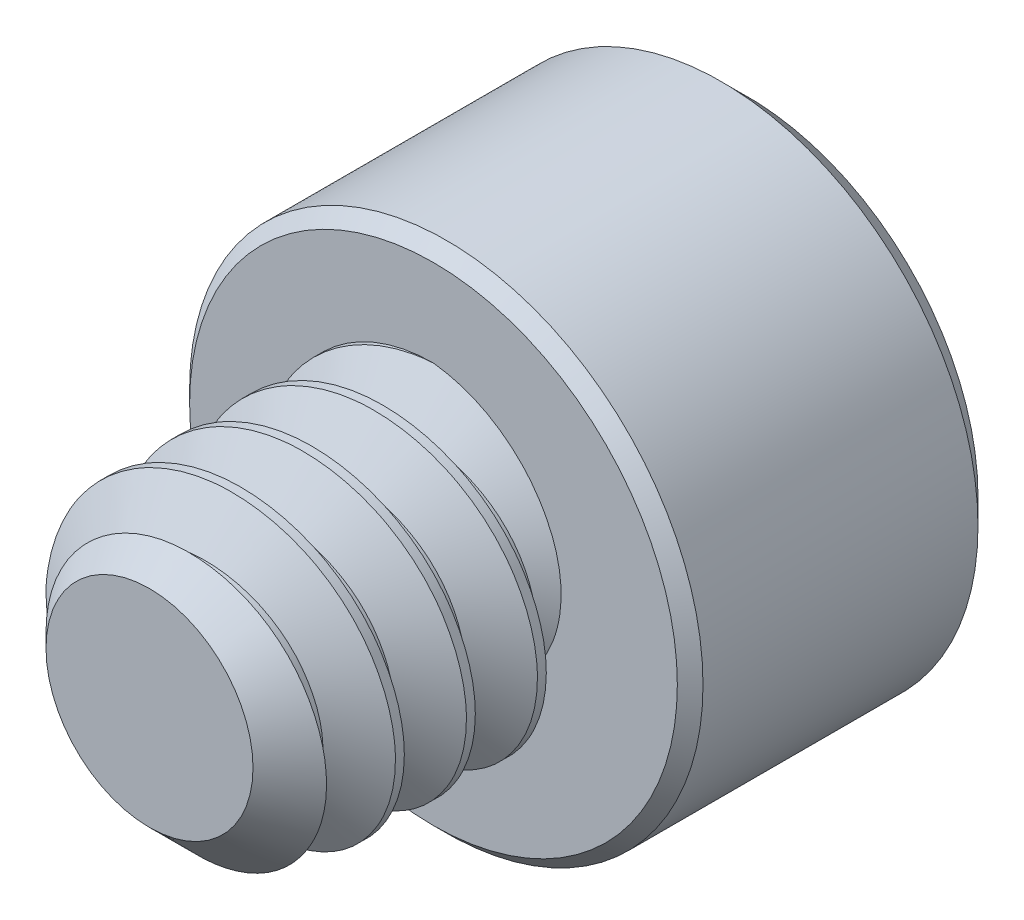
SolidWorks part; units mm, degrees
ref_plane "Front Plane" through (0, 0, 0) normal (0, 0, 1) x (1, 0, 0)
ref_plane "Top Plane" through (0, 0, 0) normal (0, 1, 0) x (1, 0, 0)
ref_plane "Right Plane" through (0, 0, 0) normal (1, 0, 0) x (0, 0, -1)
sketch "Sketch0" plane through (0, 0, 0) normal (1, 0, 0) x (0, 0, -1)
  line L0 (0, 0) -> (3.175, 0) construction
  point P2 (6.6802, 0)
  point P4 (0, 0)
  dimension "D1" = 3.175
  dimension "D2" = 3.5052
  dimension "Min Thread" = 0
sketch "Sketch1" plane through (0, 0, 0) normal (0, 0, 1) x (1, 0, 0)
  circle A0 centre (0, 0) radius 1.7526
  dimension "OD" = 3.5052
extrude "Extrude1" add sketch "Sketch1" against normal blind 3.175
sketch "Sketch2" plane through (0, 0, 0) normal (0, 0, 1) x (1, 0, 0)
  circle A0 centre (0, 0) radius 1.7526 construction
  circle A1 centre (0, 0) radius 1.7526
curve "Helix/Spiral1" pitch 0.7937 height 3.9688 turns 5 parameters "pitch"=0.7937
chamfer "Chamfer3" distance 0.5953 angle 45 1 edges at (1.7526, 0, 0)
sketch "Sketch3" plane through (0, 0, 0) normal (1, 0, 0) x (0, 0, -1)
  line L0 (-0.6945, 1.7526) -> (-0.3969, 1.237)
  line L1 (-0.3969, 1.237) -> (-0.2977, 1.237)
  line L2 (-0.2977, 1.237) -> (0, 1.7526)
  line L3 (-0.6945, 1.7526) -> (0, 1.7526)
  line L4 (-0.3473, 1.7526) -> (-0.3473, 1.237) construction
  line L5 (-0.5457, 1.4948) -> (-0.1488, 1.4948) construction
  line L6 (0, 1.7526) -> (0, -1.7526) construction
  dimension "D1" = 0.0992
  dimension "D2" = 0.3969
  dimension "D3" = 60
sweep "Cut-Sweep1" cut profiles "Sketch3" path "Helix/Spiral1"
sketch "Sketch5" plane through (0, 0, 0) normal (1, 0, 0) x (0, 0, -1)
  line L0 (3.175, -1.2539) -> (3.175, 1.2505) construction
  line L1 (3.175, 1.7526) -> (0, 1.7526)
  line L2 (3.175, 1.7526) -> (3.175, 0)
  line L3 (3.175, 0) -> (-0.6379, 0)
  line L4 (0, 0) -> (3.175, 0) construction
  line L5 (0, 1.7526) -> (-0.6379, 0)
  line L6 (0, 0) -> (5.715, 0) construction
  dimension "D1" = 70
  dimension "D3" = 2.54
revolve "partially thread" [suppressed] add sketch "Sketch5" angle 360 about L6
sketch "Sketch6" plane through (0, 0, -3.175) normal (0, 0, -1) x (-1, 0, 0)
  circle A0 centre (0, 0) radius 2.8702
  dimension "head dia" = 5.7404
extrude "Extrude2" add sketch "Sketch6" along normal blind 3.5052
sketch "Sketch7" plane through (0, 0, -6.6802) normal (0, 0, -1) x (-1, 0, 0)
  line L1 (0, 1.604) -> (-1.3891, 0.802)
  line L2 (-1.3891, 0.802) -> (-1.3891, -0.802)
  line L3 (-1.3891, -0.802) -> (0, -1.604)
  line L4 (0, -1.604) -> (1.3891, -0.802)
  line L5 (1.3891, -0.802) -> (1.3891, 0.802)
  line L6 (1.3891, 0.802) -> (0, 1.604)
  circle A0 centre (0, 0) radius 1.3891 construction
  dimension "hex dia" = 2.7781
extrude "Cut-Extrude1" cut sketch "Sketch7" against normal blind 2.0836
sketch "Sketch8" plane through (0, 0, -6.6802) normal (0, 0, -1) x (-1, 0, 0)
  circle A0 centre (0, 0) radius 1.604
extrude "Cut-Extrude2" cut sketch "Sketch8" against normal through all draft 45
chamfer "Chamfer1" distance 0.287 angle 45 1 edges at (-2.8702, 0, -6.6802)
chamfer "Chamfer2" distance 0.1435 angle 45 1 edges at (-2.8702, 0, -3.175)
sketch "Sketch9" plane through (0, 0, 0) normal (1, 0, 0) x (0, 0, -1)
  line L0 (0, 1.7526) -> (0, -1.7526) construction
  line L1 (1.9844, 1.7526) -> (1.9844, -1.7526) construction
  line L2 (6.6802, 2.8702) -> (6.6802, -2.8702) construction
  line L3 (3.175, 2.8702) -> (3.175, -2.8702) construction
  line L4 (3.175, 2.7267) -> (3.175, -2.7267) construction
  line L5 (6.6802, -2.5832) -> (6.6802, 2.5832) construction
  line L6 (3.175, -2.8702) -> (3.175, 2.8702) construction
  line L7 (0, 1.1573) -> (0, -1.1573) construction
  line L8 (-0.6945, 1.7526) -> (0, 1.7526) construction
  line L9 (1.9844, 0) -> (0, 0) construction
  dimension "D1" = 1.9844
equation "\"D3@Helix/Spiral1\" = \"screw length@Extrude1\"+\"pitch@Helix/Spiral1\""
equation "\"D1@Sketch3\" = \"pitch@Helix/Spiral1\"*.125"
equation "\"D2@Sketch3\" = \"pitch@Helix/Spiral1\"*.5"
equation "\"D1@Cut-Extrude1\" = \"hex dia@Sketch7\"*.75"
equation "\"D1@Chamfer1\" = \"head dia@Sketch6\"*.05"
equation "\"D1@Sketch9\" = \"pitch@Helix/Spiral1\"*2.50"
equation "\"D1@Chamfer2\" = \"D1@Chamfer1\"/2"
equation "\"D1@Chamfer3\" = \"pitch@Helix/Spiral1\"*.750"
equation "\"D1@Sketch0\" = \"screw length@Extrude1\""
equation "\"D2@Sketch0\" = \"head depth@Extrude2\""
